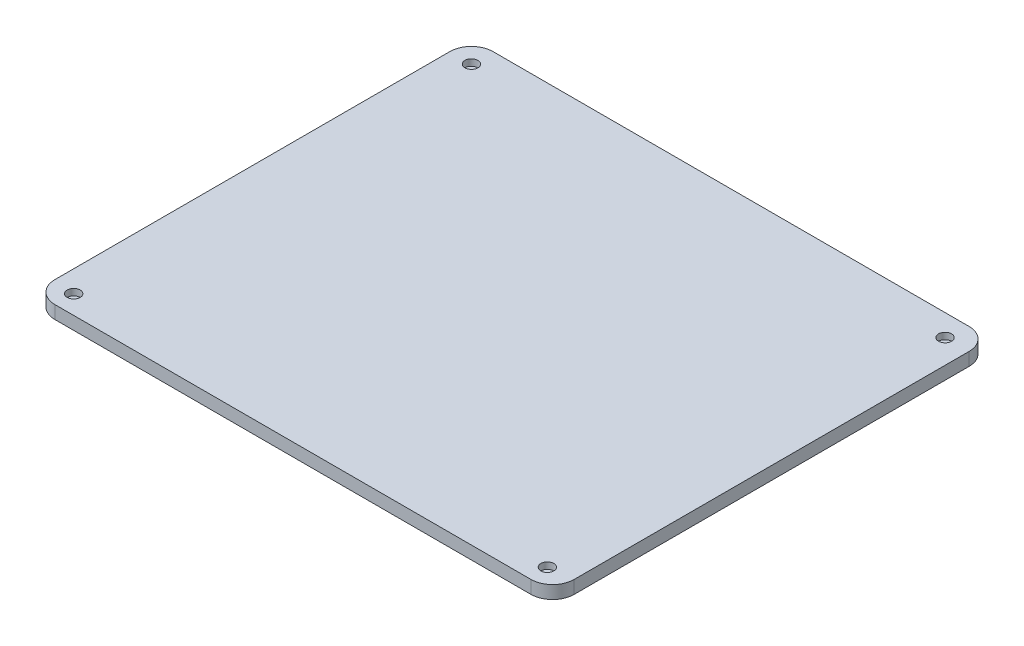
SolidWorks part; units mm, degrees
material "Vidrio"
ref_plane "Alzado" through (0, 0, 0) normal (0, 0, 1) x (1, 0, 0)
ref_plane "Planta" through (0, 0, 0) normal (0, 1, 0) x (1, 0, 0)
ref_plane "Vista lateral" through (0, 0, 0) normal (1, 0, 0) x (0, 0, -1)
sketch "Sketch1" plane through (0, 0, 0) normal (0, 1, 0) x (1, 0, 0)
  line L1 (-60, -50.625) -> (60, -50.625)
  line L2 (-60, -50.625) -> (-60, 50.625)
  line L3 (-60, 50.625) -> (60, 50.625)
  line L4 (60, -50.625) -> (60, 50.625)
  line L5 (-60, -50.625) -> (60, 50.625) construction
  line L6 (-60, 50.625) -> (60, -50.625) construction
  point P0 (0, 0)
  dimension "D1" = 120
extrude "Boss-Extrude1" add sketch "Sketch1" along normal blind 3
fillet "Fillet1" radius 5 4 edges at (-60, 1.5, -50.625) (60, 1.5, -50.625) (60, 1.5, 50.625) (-60, 1.5, 50.625)
sketch "Sketch2" plane through (0, 3, 0) normal (0, 1, 0) x (1, 0, 0)
  circle A0 centre (-55, 45.625) radius 1.5
  arc A1 (-55, 50.625) -> (-60, 45.625) centre (-55, 45.625) ccw construction
  circle A2 centre (54.4511, 45.625) radius 1.5
  circle A3 centre (-55, -46.28) radius 1.5
  circle A4 centre (54.4511, -46.28) radius 1.5
  point P11 (0, 0)
  point P12 (0, 0)
  point P13 (0, 0)
  point P14 (0, 0)
  point P15 (0, 0)
  dimension "D1" = 3
extrude "Cut-Extrude1" cut sketch "Sketch2" against normal blind 1.5
